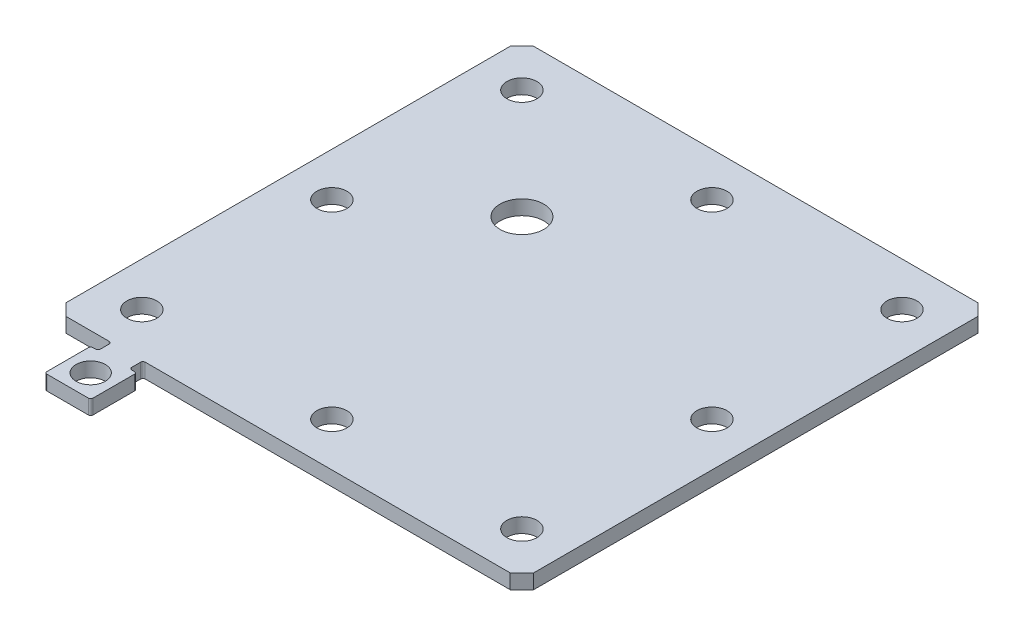
SolidWorks part; units mm, degrees
material "Commercially Pure titanium (Ti-55)  UNS R50550*"
ref_plane "Front Plane" through (0, 0, 0) normal (0, 0, 1) x (1, 0, 0)
ref_plane "Top Plane" through (0, 0, 0) normal (0, 1, 0) x (1, 0, 0)
ref_plane "Right Plane" through (0, 0, 0) normal (1, 0, 0) x (0, 0, -1)
sketch "Sketch1" plane through (0, 0, 0) normal (0, 1, 0) x (1, 0, 0)
  line L0 (45.5122, -44.6509) -> (45.5122, -53.6509)
  line L1 (46.0122, -54.1509) -> (55.0122, -54.1509)
  line L2 (55.5122, -53.6509) -> (55.5122, -44.6509)
  line L3 (55.0122, -44.1509) -> (54.4247, -44.1509)
  line L4 (53.9247, -43.6509) -> (53.9247, -41.7128)
  line L5 (54.4247, -41.2128) -> (133.6972, -41.2128)
  line L6 (133.6972, -41.2128) -> (136.2372, -38.6728)
  line L7 (136.2372, -38.6728) -> (136.2372, 57.8472)
  line L8 (136.2372, 57.8472) -> (133.6972, 60.3872)
  line L9 (133.6972, 60.3872) -> (37.1772, 60.3872)
  line L10 (37.1772, 60.3872) -> (34.6372, 57.8472)
  line L11 (34.6372, 57.8472) -> (34.6372, -38.6728)
  line L12 (34.6372, -38.6728) -> (37.1772, -41.2128)
  line L13 (37.1772, -41.2128) -> (46.5997, -41.2128)
  line L14 (47.0997, -41.7128) -> (47.0997, -43.6509)
  line L15 (46.5997, -44.1509) -> (46.0122, -44.1509)
  line L16 (34.6372, 27.0497) -> (67.9747, 27.0497) construction
  line L17 (67.9747, 27.0497) -> (67.9747, 60.3872) construction
  line L18 (46.0122, -44.6509) -> (55.0122, -53.6509) construction
  line L19 (55.0122, -44.6509) -> (46.0122, -53.6509) construction
  arc A0 (45.5122, -53.6509) -> (46.0122, -54.1509) centre (46.0122, -53.6509) ccw
  arc A1 (55.0122, -54.1509) -> (55.5122, -53.6509) centre (55.0122, -53.6509) ccw
  arc A2 (55.5122, -44.6509) -> (55.0122, -44.1509) centre (55.0122, -44.6509) ccw
  arc A3 (53.9247, -43.6509) -> (54.4247, -44.1509) centre (54.4247, -43.6509) ccw
  arc A4 (54.4247, -41.2128) -> (53.9247, -41.7128) centre (54.4247, -41.7128) ccw
  arc A5 (47.0997, -41.7128) -> (46.5997, -41.2128) centre (46.5997, -41.7128) ccw
  arc A6 (46.5997, -44.1509) -> (47.0997, -43.6509) centre (46.5997, -43.6509) ccw
  arc A7 (46.0122, -44.1509) -> (45.5122, -44.6509) centre (46.0122, -44.6509) ccw
  circle A8 centre (44.1622, 9.5872) radius 3.2639
  circle A9 centre (44.1622, -31.6878) radius 3.2639
  circle A10 centre (85.4372, -31.6878) radius 3.2639
  circle A11 centre (126.7122, -31.6878) radius 3.2639
  circle A12 centre (126.7122, 9.5872) radius 3.2639
  circle A13 centre (126.7122, 50.8622) radius 3.2639
  circle A14 centre (85.4372, 50.8622) radius 3.2639
  circle A16 centre (44.1622, 50.8622) radius 3.2639
  circle A17 centre (67.9747, 27.0497) radius 4.7625
  circle A18 centre (50.5122, -49.1509) radius 3.175
  dimension "D3" = 9.525
  dimension "D4" = 6.35
  dimension "D1" = 33.3375
  dimension "D2" = 33.3375
extrude "Boss-Extrude1" add sketch "Sketch1" along normal blind 3.175
